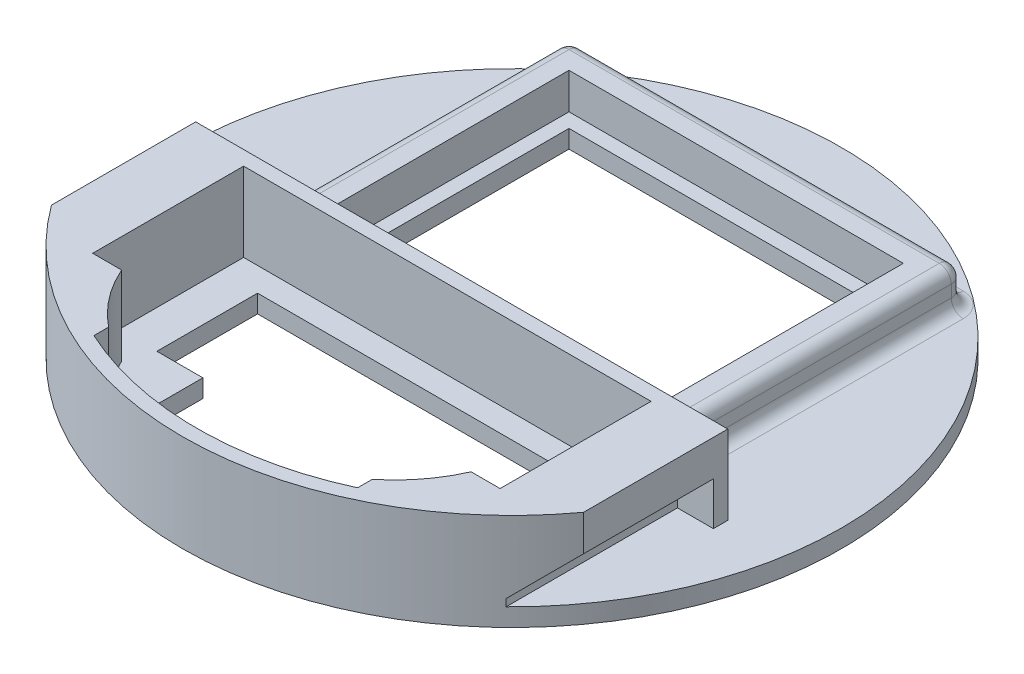
SolidWorks part; units mm, degrees
ref_plane "Front Plane" through (0, 0, 0) normal (0, 0, 1) x (1, 0, 0)
ref_plane "Top Plane" through (0, 0, 0) normal (0, 1, 0) x (1, 0, 0)
ref_plane "Right Plane" through (0, 0, 0) normal (1, 0, 0) x (0, 0, -1)
sketch "Sketch1" plane through (0, 0, 0) normal (0, 1, 0) x (1, 0, 0)
  line L0 (-16.8, 1.5) -> (16.8, 1.5) construction
  line L1 (-16.8, -6.1) -> (16.8, -6.1) construction
  line L2 (-16.8, -6.1) -> (-16.8, 6.1) construction
  line L3 (-16.8, 6.1) -> (16.8, 6.1) construction
  line L4 (16.8, -6.1) -> (16.8, 6.1) construction
  line L5 (-16.8, -6.1) -> (16.8, 6.1) construction
  line L6 (-16.8, 6.1) -> (16.8, -6.1) construction
  line L7 (0, 0) -> (0, -4) construction
  line L8 (-5, -5.4) -> (5, -5.4) construction
  line L9 (-5, -5.4) -> (-5, -2.6) construction
  line L10 (-5, -2.6) -> (5, -2.6) construction
  line L11 (5, -5.4) -> (5, -2.6) construction
  line L12 (-5, -5.4) -> (5, -2.6) construction
  line L13 (-5, -2.6) -> (5, -5.4) construction
  line L14 (0, 0) -> (0, 34.8308) construction
  line L15 (-14.772, -11.5) -> (14.772, -11.5) construction
  line L16 (-12.75, 7.1) -> (12.75, 7.1) construction
  line L17 (-12.75, 7.1) -> (-12.75, 33.2) construction
  line L18 (-12.75, 33.2) -> (12.75, 33.2) construction
  line L19 (12.75, 7.1) -> (12.75, 33.2) construction
  line L20 (-12.75, 7.1) -> (12.75, 33.2) construction
  line L21 (-12.75, 33.2) -> (12.75, 7.1) construction
  line L22 (-12.75, 12.2) -> (12.75, 12.2)
  line L23 (-12.75, 12.2) -> (-12.75, 29.2)
  line L24 (-12.75, 29.2) -> (12.75, 29.2)
  line L25 (12.75, 12.2) -> (12.75, 29.2)
  line L26 (-12.75, 12.2) -> (12.75, 29.2) construction
  line L27 (-12.75, 29.2) -> (12.75, 12.2) construction
  line L29 (-4.5, -3.6738) -> (-4.5, 4.3) construction
  line L30 (-3.5, 5.3) -> (3.5, 5.3) construction
  line L31 (4.5, -3.6738) -> (4.5, 4.3) construction
  line L32 (-15.6377, 4.3) -> (-15.6377, -1.291) construction
  line L33 (-13.8377, 6.1) -> (-7.8377, 6.1) construction
  line L35 (6.8377, -3.6738) -> (6.8377, 4.3) construction
  line L36 (7.8377, 5.3) -> (13.8377, 5.3) construction
  line L37 (14.8377, -1.291) -> (14.8377, 4.3) construction
  line L38 (6.8377, -3.6738) -> (14.8377, 5.3) construction
  line L39 (6.8377, 5.3) -> (14.8377, -1.291) construction
  line L41 (-14.8377, -1.291) -> (-14.8377, 4.3) construction
  line L42 (-13.8377, 5.3) -> (-7.8377, 5.3) construction
  line L43 (-6.8377, -3.6738) -> (-6.8377, 4.3) construction
  line L44 (-14.8377, -1.291) -> (-6.8377, 5.3) construction
  line L45 (-14.8377, 5.3) -> (-6.8377, -3.6738) construction
  line L46 (-2.8, -11.5) -> (-2, -11.5) construction
  line L47 (-5.1594, -3.6738) -> (-5.1594, 4.3) construction
  line L48 (-3.3594, 6.1) -> (3.3594, 6.1) construction
  line L49 (5.1594, -3.6738) -> (5.1594, 4.3) construction
  line L50 (2.8, -11.5) -> (2, -11.5) construction
  line L51 (-6.0377, 4.3) -> (-6.0377, -3.6738) construction
  line L52 (15.6377, -1.291) -> (15.6377, 4.3) construction
  line L53 (13.8377, 6.1) -> (7.8377, 6.1) construction
  line L54 (6.0377, 4.3) -> (6.0377, -3.6738) construction
  line L55 (-8.7689, -11.5) -> (-8.7689, -12.4022) construction
  line L56 (-4.7689, -11.5) -> (-3.8406, -11.5) construction
  line L57 (3.8406, -11.5) -> (4.7689, -11.5) construction
  line L58 (8.7689, -11.5) -> (8.7689, -12.4022) construction
  line L59 (-4.5, -3.6738) -> (4.5, -3.6738) construction
  line L60 (-12.75, 20.7) -> (12.75, 20.7) construction
  line L61 (-17, 6.3) -> (17, 6.3)
  line L62 (-17, 6.3) -> (-17, -6.3)
  line L64 (17, 6.3) -> (17, -6.3)
  line L65 (-22.2, 7.5) -> (22.2, 7.5)
  line L66 (-22.2, 7.5) -> (-22.2, -4.5343)
  line L68 (22.2, 7.5) -> (22.2, -4.5343)
  line L69 (-13.95, 30.4) -> (13.95, 30.4)
  line L70 (-13.95, 30.4) -> (-13.95, 11)
  line L71 (-13.95, 11) -> (13.95, 11)
  line L72 (13.95, 30.4) -> (13.95, 11)
  line L75 (-10, -12.629) -> (-10, -4.1)
  line L77 (-13.8377, -4.1) -> (-10, -4.1)
  line L78 (-13.8377, -4.1) -> (-13.8377, 4.3)
  line L79 (-13.8377, 4.3) -> (13.8377, 4.3)
  line L80 (13.8377, -4.1) -> (13.8377, 4.3)
  line L81 (10, -12.629) -> (10, -4.1)
  line L82 (-17, -6.3) -> (-14.5829, -6.3)
  line L83 (10, -4.1) -> (13.8377, -4.1)
  line L84 (-11, -10.971) -> (-11, -12.1935)
  line L85 (17, -6.3) -> (14.5829, -6.3)
  line L87 (11, -10.971) -> (11, -12.1935)
  line L89 (-16.45, 32.9) -> (16.45, 32.9)
  line L90 (-16.45, 32.9) -> (-16.45, 7.5)
  line L91 (-16.45, 7.5) -> (16.45, 7.5)
  line L92 (16.45, 32.9) -> (16.45, 7.5)
  circle A0 centre (11.45, 1.5) radius 2.5 construction
  circle A1 centre (0, 1.5) radius 2.5 construction
  circle A2 centre (-11.45, 1.5) radius 2.5 construction
  circle A3 centre (0, 11.6956) radius 25 construction
  circle A4 centre (0, 11.6956) radius 27.5
  arc A5 (-14.8377, -1.291) -> (-8.7689, -11.5) centre (-3.2164, -1.291) ccw construction
  arc A6 (-6.8377, -3.6738) -> (-4.7689, -11.5) centre (9, -3.6738) ccw construction
  arc A7 (4.5, -3.6738) -> (2, -11.5) centre (-9, -3.6738) cw construction
  arc A8 (-4.5, -3.6738) -> (-2, -11.5) centre (9, -3.6738) ccw construction
  arc A9 (6.8377, -3.6738) -> (4.7689, -11.5) centre (-9, -3.6738) cw construction
  arc A10 (14.8377, -1.291) -> (8.7689, -11.5) centre (3.2164, -1.291) cw construction
  arc A11 (4.5, 4.3) -> (3.5, 5.3) centre (3.5, 4.3) ccw construction
  arc A12 (-3.5, 5.3) -> (-4.5, 4.3) centre (-3.5, 4.3) ccw construction
  arc A13 (-2.8, -11.5) -> (-5.1594, -3.6738) centre (9, -3.6738) cw construction
  arc A14 (-3.3594, 6.1) -> (-5.1594, 4.3) centre (-3.3594, 4.3) ccw construction
  arc A15 (3.3594, 6.1) -> (5.1594, 4.3) centre (3.3594, 4.3) cw construction
  arc A16 (2.8, -11.5) -> (5.1594, -3.6738) centre (-9, -3.6738) ccw construction
  arc A17 (-15.6377, -1.291) -> (-8.7689, -12.4022) centre (-3.2164, -1.291) ccw construction
  arc A18 (-6.0377, -3.6738) -> (-3.8406, -11.5) centre (9, -3.6738) ccw construction
  arc A19 (6.0377, -3.6738) -> (3.8406, -11.5) centre (-9, -3.6738) cw construction
  arc A20 (15.6377, -1.291) -> (8.7689, -12.4022) centre (3.2164, -1.291) cw construction
  arc A21 (-6.8377, 4.3) -> (-7.8377, 5.3) centre (-7.8377, 4.3) ccw construction
  arc A22 (-13.8377, 5.3) -> (-14.8377, 4.3) centre (-13.8377, 4.3) ccw construction
  arc A23 (15.6377, 4.3) -> (13.8377, 6.1) centre (13.8377, 4.3) ccw construction
  arc A24 (7.8377, 6.1) -> (6.0377, 4.3) centre (7.8377, 4.3) ccw construction
  arc A25 (-6.0377, 4.3) -> (-7.8377, 6.1) centre (-7.8377, 4.3) ccw construction
  arc A26 (-13.8377, 6.1) -> (-15.6377, 4.3) centre (-13.8377, 4.3) ccw construction
  arc A27 (14.8377, 4.3) -> (13.8377, 5.3) centre (13.8377, 4.3) ccw construction
  arc A28 (7.8377, 5.3) -> (6.8377, 4.3) centre (7.8377, 4.3) ccw construction
  arc A35 (-11, -12.1935) -> (11, -12.1935) centre (0, 11.6956) ccw
  arc A36 (-14.5829, -6.3) -> (-11, -10.971) centre (-3.2164, -1.291) ccw
  arc A37 (14.5829, -6.3) -> (11, -10.971) centre (3.2164, -1.291) cw
  point P0 (0, 0)
  point P16 (0, -4)
  point P21 (0, 20.15)
  point P29 (0, 20.7)
  point P66 (0, 6.1)
  dimension "D6" = 28.25
  dimension "D7" = 5
  dimension "D11" = 50
  dimension "D18" = 55
  dimension "D19" = 18
  dimension "D20" = 4
  dimension "D21" = 1
  dimension "D24" = 1.8
  dimension "D36" = 1
  dimension "D40" = 1.8
  dimension "D41" = 1
  dimension "D30" = 1.2
  dimension "D1" = 12.2
  dimension "D2" = 33.6
  dimension "D3" = 4.6
  dimension "D4" = 5.35
  dimension "D5" = 16.8
  dimension "D8" = 10
  dimension "D9" = 3.5
  dimension "D10" = 0.7
  dimension "D12" = 26.1
  dimension "D13" = 25.5
  dimension "D14" = 1
  dimension "D15" = 4
  dimension "D16" = 17
  dimension "D17" = 13
  dimension "D22" = 0.8
  dimension "D23" = 0.8
  dimension "D25" = 9
  dimension "D26" = 8
  dimension "D27" = 0.2
  dimension "D28" = 0.2
  dimension "D29" = 8
  dimension "D31" = 4
  dimension "D32" = 4
  dimension "D33" = 0.8
  dimension "D34" = 0.8
  dimension "D35" = 0.8
  dimension "D37" = 0.8
  dimension "D38" = 0.8
  dimension "D39" = 0.8
  dimension "D42" = 44.4
  dimension "D43" = 1.2
  dimension "D44" = 2
  dimension "D45" = 1.2
  dimension "D46" = 1.2
  dimension "D47" = 0.2
  dimension "D48" = 7
  dimension "D49" = 6
  dimension "D50" = 2.5
  dimension "D51" = 2.5
extrude "Boss-Extrude1" add sketch "Sketch1" against normal blind 1.5 contours L72 L69 L70 L71 L25 L22 L23 L24 | L92 L89 L90 L91 L69 L72 L71 L70 | L68 A4 L66 L65 L89 L92 L91 L90 | L66 A4 L68 L65 L85 A37 L87 A35 L84 A36 L82 L62 L61 L64 | A37 L85 L64 L61 L62 L82 A36 L84 A35 L75 L77 L78 L79 L80 L83 L81 L87 region at (0, 0, -5.9109) region at (-22.9027, 0, -1.4829) region at (-19.325, 0, -6.9986) region at (-16.0344, 0, -20.2) region at (0, 0, -30.0602)
extrude "Boss-Extrude2" add sketch "Sketch1<3>" along normal blind 6.6 contours L68 L65 L66 L62 L61 L64 region at (-19.325, 0, -6.9986)
sketch "Sketch1<3>" plane through (0, 0, 0) normal (0, 1, 0) x (1, 0, 0) same geometry as "Sketch1"
sketch "Sketch2" plane through (0, 0, -6.3) normal (0, 0, 1) x (1, 0, 0)
  line L0 (-22.2, 3.6) -> (-19.2, 0.6)
  line L1 (-22.2, 6.6) -> (-22.2, 0) construction
  line L2 (-19.2, 0.6) -> (-19.2, 0)
  line L3 (-19.2, 0) -> (-22.2, 0)
  line L4 (0, 0) -> (0, 16.7972) construction
  line L5 (-22.2, 3.6) -> (-22.2, 0)
  line L6 (19.2, 0.6) -> (19.2, 0)
  line L7 (22.2, 3.6) -> (22.2, 0)
  line L8 (22.2, 3.6) -> (19.2, 0.6)
  line L9 (19.2, 0) -> (22.2, 0)
  line L10 (22.2, 6.6) -> (-22.2, 6.6) construction
  dimension "D1" = 45
  dimension "D2" = 0.6
  dimension "D3" = 3
  dimension "D4" = 3
extrude "Cut-Extrude1" cut sketch "Sketch2" along normal up to next contours L5 L3 L2 L0 | L6 L9 L7 L8
extrude "Boss-Extrude3" add sketch "Sketch1<5>" along normal blind 3 contours L92 L89 L90 L91 L69 L72 L71 L70 region at (-16.0344, 0, -20.2)
sketch "Sketch1<5>" plane through (0, 0, 0) normal (0, 1, 0) x (1, 0, 0) same geometry as "Sketch1"
fillet "Fillet1" radius 1 11 edges at (-16.45, 3, -20.2) (-16.45, 0, -20.2) (16.45, 3, -20.2) (16.45, 0, -20.2) (16.45, 1.5, -32.9) (0, 3, -32.9) (-16.45, 1.5, -32.9) (0, 0, -32.9) (0, 3, -7.5) (-16.45, 1.5, -7.5) (16.45, 1.5, -7.5)
